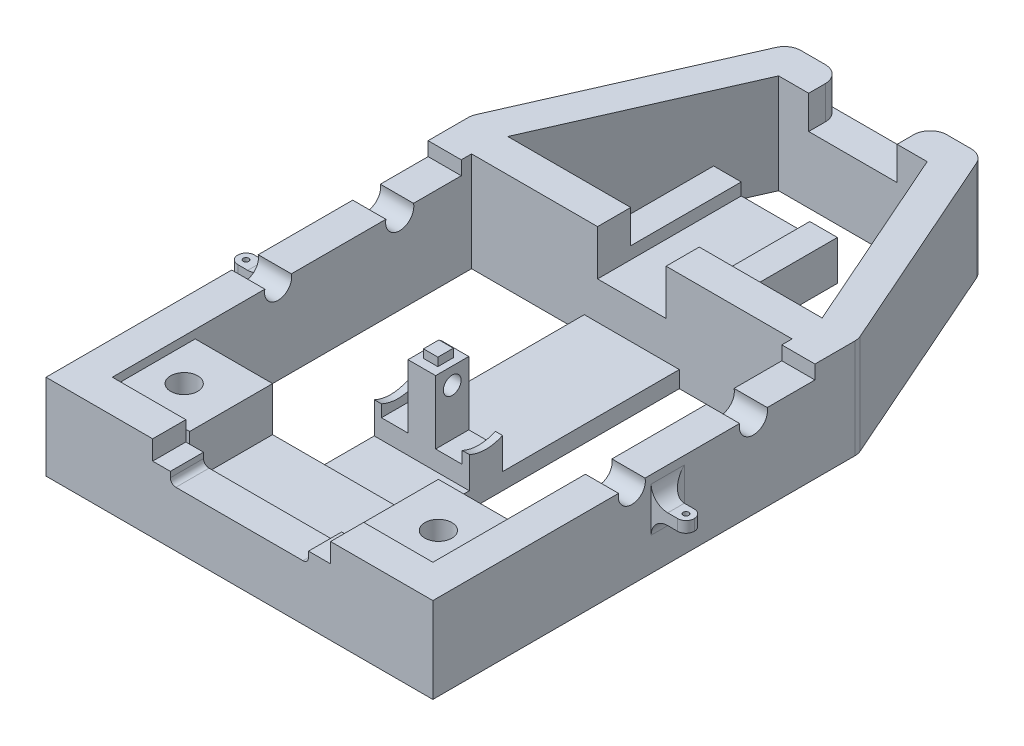
SolidWorks part; units mm, degrees
ref_plane "Front Plane" through (0, 0, 0) normal (0, 0, 1) x (1, 0, 0)
ref_plane "Top Plane" through (0, 0, 0) normal (0, 1, 0) x (1, 0, 0)
ref_plane "Right Plane" through (0, 0, 0) normal (1, 0, 0) x (0, 0, -1)
sketch "Sketch1" plane through (0, 0, 0) normal (0, 1, 0) x (1, 0, 0)
  line L0 (-35, 38.5) -> (-17.3529, 78.5)
  line L1 (-29, 32.5) -> (29, 32.5)
  line L2 (-29, 32.5) -> (-29, -32.5)
  line L3 (-29, -32.5) -> (29, -32.5)
  line L4 (29, 32.5) -> (29, -32.5)
  line L5 (-29, 32.5) -> (29, -32.5) construction
  line L6 (-29, -32.5) -> (29, 32.5) construction
  line L7 (-28.442, 38.5) -> (28.442, 38.5)
  line L8 (-35, 38.5) -> (-35, -38.5)
  line L9 (-35, -38.5) -> (35, -38.5)
  line L10 (35, 38.5) -> (35, -38.5)
  line L11 (-35, 38.5) -> (35, -38.5) construction
  line L12 (-35, -38.5) -> (35, 38.5) construction
  line L13 (-17.3529, 78.5) -> (17.3529, 78.5)
  line L14 (17.3529, 78.5) -> (35, 38.5)
  line L15 (-28.442, 38.5) -> (-13.442, 72.5)
  line L16 (-13.442, 72.5) -> (13.442, 72.5)
  line L17 (13.442, 72.5) -> (28.442, 38.5)
  point P0 (0, 0)
  point P6 (0, 0)
  point P15 (0, 72.5)
  point P18 (0, 38.5)
  dimension "D1" = 58
  dimension "D2" = 6
  dimension "D3" = 6
  dimension "D4" = 65
  dimension "D5" = 40
  dimension "D6" = 6
  dimension "D7" = 6
  dimension "D8" = 6
  dimension "D9" = 34
  dimension "D10" = 15
  dimension "D11" = 6
  dimension "D12" = 6
extrude "Boss-Extrude1" add sketch "Sketch1" along normal blind 30
ref_plane "Plane1" through (0, 0, 5.5) normal (0, 0, 1) x (1, 0, 0)
ref_plane "Plane2" through (0, 15, 0) normal (0, -1, 0) x (-1, 0, 0)
sketch "Sketch7" plane through (0, 0, -32.5) normal (0, 0, 1) x (1, 0, 0)
  line L0 (-35, 30) -> (35, 30) construction
  line L1 (-8.6, 30) -> (8.6, 30)
  line L2 (-8.6, 30) -> (-8.6, 27)
  line L3 (-8.6, 27) -> (8.6, 27)
  line L4 (8.6, 30) -> (8.6, 27)
  line L6 (-35, 30) -> (-35, 0) construction
  point P6 (0, 30)
  dimension "D1" = 3
  dimension "D2" = 17.2
  dimension "D3" = 35
sketch "Sketch8" plane through (0, 0, 5.5) normal (0, 0, 1) x (1, 0, 0)
  line L0 (-8.6, 30) -> (8.6, 30) construction
  line L1 (-8.6, 30) -> (8.6, 30)
  line L2 (-8.6, 30) -> (-8.6, 27)
  line L3 (-8.6, 27) -> (8.6, 27)
  line L4 (8.6, 30) -> (8.6, 27)
  line L5 (-8.6, 27) -> (8.6, 27) construction
sketch "Sketch9" plane through (0, 30, 0) normal (0, 1, 0) x (1, 0, 0)
  line L0 (10, 32.5) -> (2.5, -5.5)
  line L1 (-8.6, 32.5) -> (8.6, 32.5) construction
  line L2 (-8.6, -5.5) -> (8.6, -5.5) construction
  line L3 (-16.5058, -5.5) -> (16.5058, -5.5) construction
  line L4 (-10, 32.5) -> (-2.5, -5.5)
loft "Loft3" add profiles "Sketch7", "Sketch8"
mirror "Mirror3" about plane through (0, 15, 0) normal (0, -1, 0) of "Loft3"
sketch "Sketch10" plane through (0, 27, 0) normal (0, -1, 0) x (1, 0, 0)
  line L0 (-8.6, -32.5) -> (8.6, -32.5) construction
  line L1 (-2.5, 5.5) -> (2.5, 5.5)
  line L2 (-2.5, 5.5) -> (-2.5, -0.5)
  line L3 (-2.5, -0.5) -> (2.5, -0.5)
  line L4 (2.5, 5.5) -> (2.5, -0.5)
  line L6 (-8.6, 5.5) -> (8.6, 5.5) construction
  point P5 (2.5, 2.5)
  point P10 (0, 5.5)
  point P11 (0, 5.5)
  dimension "D1" = 5
  dimension "D2" = 35
  dimension "D3" = 0
  dimension "D4" = 0
extrude "Boss-Extrude3" add sketch "Sketch10" along normal up to next
sketch "Sketch2" plane through (35, 0, 0) normal (1, 0, 0) x (0, 0, -1)
  line L0 (38.5, 30) -> (38.5, 0) construction
  line L1 (-38.5, 30) -> (38.5, 30) construction
  circle A0 centre (-2.5, 15) radius 2.45
  circle A1 centre (19.5, 15) radius 2.55
  dimension "D2" = 15
  dimension "D3" = 4.9
  dimension "D5" = 5.1
  dimension "D1" = 19
  dimension "D4" = 22
extrude "Cut-Extrude1" cut sketch "Sketch2" against normal up to next
sketch "Sketch3" plane through (0, 0, -38.5) normal (0, 0, -1) x (-1, 0, 0)
  line L1 (-6.2, 20.2) -> (6.2, 20.2)
  line L2 (-6.2, 20.2) -> (-6.2, 9.8)
  line L3 (-6.2, 9.8) -> (6.2, 9.8)
  line L4 (6.2, 20.2) -> (6.2, 9.8)
  line L5 (-6.2, 20.2) -> (6.2, 9.8) construction
  line L6 (-6.2, 9.8) -> (6.2, 20.2) construction
  line L7 (-17.3529, 0) -> (17.3529, 0) construction
  line L9 (35, 30) -> (35, 0) construction
  point P0 (0, 15)
  dimension "D1" = 10.4
  dimension "D2" = 12.4
  dimension "D3" = 35
  dimension "D4" = 15
extrude "Cut-Extrude2" cut sketch "Sketch3" against normal up to next
sketch "Sketch11" plane through (35, 0, 0) normal (1, 0, 0) x (0, 0, -1)
  line L0 (-2.5, 15) -> (72.7738, 15) construction
  line L1 (1, 19) -> (4, 19)
  line L2 (1, 19) -> (1, 21)
  line L3 (1, 21) -> (4, 21)
  line L4 (4, 19) -> (4, 21)
  line L5 (4, 11) -> (4, 9)
  line L6 (1, 9) -> (4, 9)
  line L7 (1, 11) -> (1, 9)
  line L8 (1, 11) -> (4, 11)
  point P7 (2.5, 19)
  dimension "D1" = 3
  dimension "D2" = 2
  dimension "D3" = 6
  dimension "D4" = 5
extrude "Boss-Extrude4" add sketch "Sketch11" along normal blind 6.3
fillet "Fillet3" radius 1.5 4 edges at (41.3, 10, -1) (41.3, 10, -4) (41.3, 20, -1) (41.3, 20, -4)
sketch "Sketch12" plane through (0, 21, 0) normal (0, 1, 0) x (1, 0, 0)
  circle A0 centre (39.8, 2.5) radius 0.5
extrude "Cut-Extrude3" cut sketch "Sketch12" against normal through all
ref_plane "Plane3" through (0, 0, 0) normal (1, 0, 0) x (0, 0, -1)
mirror "Mirror1" about plane through (0, 0, 0) normal (1, 0, 0) of "Cut-Extrude1", "Boss-Extrude4", "Fillet3", "Cut-Extrude3"
sketch "Sketch13" plane through (-29, 0, 0) normal (1, 0, 0) x (0, 0, -1)
  line L1 (-32.5, 30) -> (-17.5, 30)
  line L2 (-32.5, 30) -> (-32.5, 24)
  line L3 (-32.5, 24) -> (-17.5, 24)
  line L4 (-17.5, 30) -> (-17.5, 24)
  dimension "D1" = 6
  dimension "D2" = 15
extrude "Boss-Extrude5" add sketch "Sketch13" along normal up to next
sketch "Sketch17" plane through (-29, 0, 0) normal (1, 0, 0) x (0, 0, -1)
  line L0 (32.5, 0) -> (-32.5, 0) construction
  line L1 (-32.5, 0) -> (-17.5, 0)
  line L2 (-32.5, 0) -> (-32.5, 14)
  line L3 (-32.5, 14) -> (-17.5, 14)
  line L4 (-17.5, 0) -> (-17.5, 14)
  dimension "D1" = 14
  dimension "D2" = 15
extrude "Boss-Extrude6" add sketch "Sketch17" along normal up to next
sketch "Sketch14" plane through (0, 30, 0) normal (0, 1, 0) x (1, 0, 0)
  line L0 (-35, 38.5) -> (-35, -38.5) construction
  line L1 (35, -38.5) -> (35, 38.5) construction
  line L2 (-35, -38.5) -> (35, -38.5) construction
  circle A0 centre (-23, -25.5) radius 2.45
  circle A1 centre (23, -25.5) radius 2.45
  dimension "D5" = 4.9
  dimension "D6" = 4.9
  dimension "D1" = 12
  dimension "D2" = 12
  dimension "D3" = 13
  dimension "D4" = 0
extrude "Cut-Extrude4" cut sketch "Sketch14" against normal through all
sketch "Sketch16" plane through (35, 0, 0) normal (1, 0, 0) x (0, 0, -1)
  line L0 (-38.5, 30) -> (-38.5, 0) construction
  line L7 (-38.5, 22.5) -> (-22.5, 22.5)
  line L8 (-38.5, 22.5) -> (-38.5, 15.5)
  line L9 (-38.5, 15.5) -> (-22.5, 15.5)
  line L10 (-22.5, 22.5) -> (-22.5, 15.5)
  line L11 (-38.5, 30) -> (38.5, 30) construction
  dimension "D1" = 7.5
  dimension "D2" = 7
  dimension "D3" = 16
extrude "Cut-Extrude7" cut sketch "Sketch16" against normal blind 15
mirror "Mirror2" about plane through (0, 0, 0) normal (1, 0, 0) of "Cut-Extrude7"
sketch "Sketch18" plane through (0, 0, 38.5) normal (0, 0, 1) x (1, 0, 0)
  line L0 (0, -16.5) -> (0, 16.5) construction
  line L3 (-35, 0) -> (35, 0) construction
  line L4 (-11.5, 14) -> (11.5, 14)
  line L5 (-11.5, 10) -> (11.5, 10)
  line L6 (-12.5, 13) -> (-12.5, 11)
  line L7 (12.5, 11) -> (12.5, 13)
  arc A2 (12.5, 11) -> (11.5, 10) centre (11.5, 11) cw
  arc A3 (12.5, 13) -> (11.5, 14) centre (11.5, 13) ccw
  arc A4 (-11.5, 10) -> (-12.5, 11) centre (-11.5, 11) cw
  arc A5 (-11.5, 14) -> (-12.5, 13) centre (-11.5, 13) ccw
  point P0 (0, 14)
  point P12 (12.5, 10)
  point P15 (12.5, 14)
  point P20 (-12.5, 14)
  dimension "D2" = 10
  dimension "D5" = 1
  dimension "D1" = 4
  dimension "D3" = 25
  dimension "D4" = 0
extrude "Cut-Extrude8" cut sketch "Sketch18" against normal up to next
sketch "Sketch19" plane through (0, 30, 0) normal (0, 1, 0) x (1, 0, 0)
  line L0 (29, -17.5) -> (-29, -17.5) construction
  line L1 (-15, -17.5) -> (15, -17.5)
  line L2 (-15, -17.5) -> (-15, -32.5)
  line L3 (-15, -32.5) -> (15, -32.5)
  line L4 (15, -17.5) -> (15, -32.5)
  line L5 (-35, -38.5) -> (35, -38.5) construction
  line L6 (-35, 38.5) -> (-35, -38.5) construction
  line L7 (35, -38.5) -> (35, 38.5) construction
  dimension "D1" = 6
  dimension "D2" = 20
  dimension "D3" = 20
extrude "Cut-Extrude9" cut sketch "Sketch19" against normal offset from surface (18 mm away) 6 from offset 6 up to face at (-23, 0, 27.95) offset against normal yes
sketch "Sketch35" plane through (0, 0, -78.5) normal (0, 0, -1) x (-1, 0, 0)
  line L0 (0, 0) -> (0, 30) construction
  line L1 (28.442, 30) -> (-28.442, 30) construction
  line L3 (-8, 18) -> (8, 18)
  line L4 (-8, 18) -> (-8, 12)
  line L5 (-8, 12) -> (8, 12)
  line L6 (8, 18) -> (8, 12)
  line L7 (-8, 18) -> (8, 12) construction
  line L8 (-8, 12) -> (8, 18) construction
  point P5 (0, 15)
  dimension "D1" = 16
  dimension "D2" = 6
extrude "Cut-Extrude18" cut sketch "Sketch35" against normal up to next
fillet "Fillet5" radius 3 6 edges at (-35, 15, -38.5) (-17.3529, 15, -78.5) (-8, 15, -78.5) (8, 15, -78.5) (17.3529, 15, -78.5) (35, 15, -38.5)
sketch "Sketch24" plane through (0, 0, 0) normal (0, 1, 0) x (1, 0, 0)
  line L0 (13.442, 72.5) -> (-13.442, 72.5) construction
  line L1 (-23.5891, 49.5) -> (-9.15, 49.5)
  line L3 (-26.2362, 43.5) -> (26.2362, 43.5)
  line L5 (28.442, 38.5) -> (13.442, 72.5) construction
  line L7 (-6.15, 49.5) -> (-6.15, 72.5)
  line L9 (6.15, 49.5) -> (6.15, 72.5)
  line L10 (-13.442, 72.5) -> (-28.442, 38.5) construction
  line L11 (26.2362, 43.5) -> (22.3466, 52.3162)
  line L12 (-23.5891, 49.5) -> (-26.2362, 43.5)
  line L13 (-6.15, 49.5) -> (6.15, 49.5)
  line L15 (-9.15, 49.5) -> (-9.15, 72.5)
  line L16 (-9.15, 72.5) -> (-6.15, 72.5)
  line L17 (-6.15, 49.5) -> (-6.15, 72.5)
  line L19 (6.15, 49.5) -> (6.15, 72.5)
  line L20 (6.15, 72.5) -> (9.15, 72.5)
  line L21 (9.15, 52.5) -> (9.15, 72.5)
  line L22 (9.15, 52.5) -> (22.3466, 52.3162)
  point P10 (0, 49.5)
  point P12 (0, 43.5)
  point P13 (0, 72.5)
  dimension "D1" = 23
  dimension "D2" = 6
  dimension "D4" = 0
  dimension "D5" = 12.3
  dimension "D7" = 3
  dimension "D8" = 3
extrude "Boss-Extrude7" add sketch "Sketch24" along normal up to surface (9.8 mm away) from offset 30 contours L21 L22 L11 L3 L12 L1 L15 L16 L7 L13 L9 L20
sketch "Sketch23" plane through (0, 12, 0) normal (0, 1, 0) x (1, 0, 0)
  line L1 (-6.15, 72.5) -> (6.15, 72.5)
  line L2 (-6.15, 72.5) -> (-6.15, 78.5)
  line L3 (-6.15, 78.5) -> (6.15, 78.5)
  line L4 (6.15, 72.5) -> (6.15, 78.5)
  line L5 (15.3975, 78.5) -> (-15.3975, 78.5) construction
  line L6 (-26.2362, 43.5) -> (26.2362, 43.5) construction
  line L7 (-6.15, 49.5) -> (6.15, 49.5)
  line L8 (-6.15, 49.5) -> (-6.15, 43.5)
  line L9 (-6.15, 43.5) -> (6.15, 43.5)
  line L10 (6.15, 49.5) -> (6.15, 43.5)
  point P8 (0, 78.5)
  point P9 (0, 72.5)
  dimension "D2" = 0
extrude "Cut-Extrude12" cut sketch "Sketch23" along normal up to next from offset 16.5
sketch "Sketch26" plane through (0, 0, -38.5) normal (0, 0, -1) x (-1, 0, 0)
  line L0 (-6.2, 9.8) -> (6.2, 9.8) construction
  line L1 (6.2, 9.8) -> (6.2, 20.2) construction
  line L2 (11, 12) -> (8, 12) construction
  line L3 (-6.2, 20.2) -> (-6.2, 9.8) construction
  line L4 (-6.2, 9.8) -> (6.2, 9.8)
  line L5 (6.2, 9.8) -> (6.2, 12)
  line L7 (-6.2, 12) -> (-6.2, 9.8)
  line L8 (-11.2, 4.8) -> (11.2, 4.8)
  line L9 (11.2, 4.8) -> (11.2, 12)
  line L11 (-11.2, 12) -> (-11.2, 4.8)
  line L12 (-11.2, 12) -> (-6.2, 12)
  line L14 (6.2, 12) -> (11.2, 12)
  line L15 (-11.2, 25.2) -> (-11.2, 4.8) construction
  line L16 (11.2, 25.2) -> (-11.2, 25.2) construction
  line L17 (6.2, 20.2) -> (-6.2, 20.2) construction
  line L18 (-6.2, 20.2) -> (-6.2, 9.8) construction
  line L19 (6.2, 9.8) -> (6.2, 20.2) construction
  line L20 (11.2, 4.8) -> (11.2, 25.2) construction
  line L21 (-11, 12) -> (11, 12) construction
  dimension "D1" = 5
extrude "Boss-Extrude8" add sketch "Sketch26" along normal blind 20
sketch "Sketch28" plane through (0, 28.5, 0) normal (0, 1, 0) x (-1, 0, 0)
  line L0 (0, 16.5) -> (0, -16.5) construction
  line L1 (0.4, -44) -> (6, -44) construction
  line L2 (0.4, -78) -> (6, -78) construction
  circle A0 centre (0, -46.5) radius 0.8
  circle A1 centre (0, -75.5) radius 0.8
  dimension "D2" = 1.6
  dimension "D3" = 1.6
  dimension "D1" = 2.5
  dimension "D4" = 2.5
extrude "Cut-Extrude15" cut sketch "Sketch28" against normal up to next
fillet "Fillet4" radius 3 12 edges at (35, 9, -2.5) (35, 11, -2.5) (35, 21, -2.5) (35, 19, -2.5) (35, 20, -4) (35, 10, -4) (-35, 9, -2.5) (-35, 10, -4) (-35, 11, -2.5) (-35, 19, -2.5) (-35, 20, -4) (-35, 21, -2.5)
sketch "Sketch29" plane through (2.5, 0, 0) normal (1, 0, 0) x (0, 0, -1)
  circle A0 centre (-2.5, 15) radius 1.6
  dimension "D1" = 3.2
extrude "Cut-Extrude16" cut sketch "Sketch29" against normal up to next
sketch "Sketch30" plane through (-2.5, 0, 0) normal (-1, 0, 0) x (0, 0, 1)
  line L0 (-32.5, 27) -> (5.5, 27) construction
  line L1 (-0.5, 27) -> (5.5, 27)
  line L2 (-0.5, 27) -> (-0.5, 23.5)
  line L3 (-0.5, 23.5) -> (5.5, 23.5)
  line L4 (5.5, 27) -> (5.5, 23.5)
  line L5 (-0.5, 3) -> (-0.5, 27) construction
  line L6 (5.5, 3) -> (5.5, 27) construction
  dimension "D1" = 3.5
extrude "Boss-Extrude9" add sketch "Sketch30" along normal blind 6.1
sketch "Sketch31" plane through (0, 23.5, 0) normal (0, -1, 0) x (1, 0, 0)
  line L0 (-8.6, -0.5) -> (-2.5, -0.5) construction
  line L1 (-8.6, 5.5) -> (-7.3, 5.5)
  line L2 (-8.6, 5.5) -> (-8.6, -0.5)
  line L3 (-8.6, -0.5) -> (-7.3, -0.5)
  line L4 (-7.3, 5.5) -> (-7.3, -0.5)
  dimension "D1" = 1.3
extrude "Boss-Extrude10" add sketch "Sketch31" along normal blind 5
sketch "Sketch32" plane through (-8.6, 0, 0) normal (-1, 0, 0) x (0, 0, 1)
  line L0 (-0.5, 18.5) -> (-0.5, 21.3246)
  line L1 (-0.5, 27) -> (-0.5, 18.5) construction
  line L2 (-0.5, 18.5) -> (5.5, 18.5)
  line L3 (5.5, 18.5) -> (5.5, 21.3246)
  line L4 (5.5, 18.5) -> (5.5, 27) construction
  arc A2 (5.5, 21.3246) -> (-0.5, 21.3246) centre (2.5, 15) ccw
  dimension "D1" = 7
extrude "Cut-Extrude17" cut sketch "Sketch32" against normal up to next
mirror "Mirror4" about plane through (0, 15, 0) normal (0, -1, 0) of "Cut-Extrude17", "Boss-Extrude10", "Boss-Extrude9"
mirror "Mirror5" about plane through (0, 0, 0) normal (1, 0, 0) of "Mirror4", "Cut-Extrude17", "Boss-Extrude10", "Boss-Extrude9"
sketch "Sketch33" plane through (0, 0, 5.5) normal (0, 0, 1) x (1, 0, 0)
  line L1 (-8.6, 30) -> (8.6, 30)
  line L2 (-8.6, 30) -> (-8.6, 27)
  line L3 (-8.6, 27) -> (8.6, 27)
  line L4 (8.6, 30) -> (8.6, 27)
  dimension "D1" = 3
sketch "Sketch34" plane through (0, 0, 17.5) normal (0, 0, -1) x (-1, 0, 0)
  line L0 (-29, 30) -> (29, 30) construction
  line L1 (-8.6, 30) -> (8.6, 30)
  line L2 (-8.6, 30) -> (-8.6, 27)
  line L3 (-8.6, 27) -> (8.6, 27)
  line L4 (8.6, 30) -> (8.6, 27)
  line L5 (0, 16.5) -> (0, -16.5) construction
  point P6 (0, 27)
  dimension "D3" = 0
loft "Loft4" add profiles "Sketch33", "Sketch34"
mirror "Mirror6" about plane through (0, 15, 0) normal (0, -1, 0) of "Loft4"
sketch3d "Cut_line"
  line L0 (35, 18, -78.5) -> (35, 18, -30.637)
  line L1 (35, 15.5, 38.5) -> (35, 15.5, -30.637)
  line L2 (35, 15.5, -30.637) -> (35, 18, -30.637)
  line L3 (35, 15.5, 38.5) -> (16.4919, 15.5, 38.5)
  line L4 (12.5, 12, 38.5) -> (16.4919, 12, 38.5)
  line L5 (12.5, 11, 38.5) -> (12.5, 13, 38.5) construction
  line L6 (16.4919, 12, 38.5) -> (16.4919, 15.5, 38.5)
  line L7 (12.5, 12, 38.5) -> (-15.6959, 12, 38.5)
  line L8 (-15.6959, 12, 38.5) -> (-15.6959, 15.5, 38.5)
  line L9 (-15.6959, 15.5, 38.5) -> (-35, 15.5, 38.5)
  line L10 (35, 18, -78.5) -> (-35, 18, -78.5)
  line L11 (-35, 18, -78.5) -> (-35, 18, -30.637)
  line L12 (-35, 18, -30.637) -> (-35, 15.5, -30.637)
  line L13 (-35, 15.5, -30.637) -> (-35, 15.5, 38.5)
  line L14 (-11, 18, -78.5) -> (11, 18, -78.5) construction
  dimension "D1" = 0
sketch "Sketch36" plane through (0, 30, 0) normal (0, 1, 0) x (1, 0, 0)
  line L1 (-79.7704, 95.6479) -> (84.8882, 95.6479)
  line L2 (-79.7704, 95.6479) -> (-79.7704, -54.2142)
  line L3 (-79.7704, -54.2142) -> (84.8882, -54.2142)
  line L4 (84.8882, 95.6479) -> (84.8882, -54.2142)
extrude "Cut-Extrude19" cut sketch "Sketch36" against normal blind 12
sketch "Sketch37" plane through (0, 18, 0) normal (0, 1, 0) x (1, 0, 0)
  line L1 (35, 30.637) -> (-54.071, 30.637)
  line L3 (35, -45.1136) -> (-54.071, -45.1136)
  line L4 (-54.071, 30.637) -> (-54.071, -45.1136)
  line L5 (35, 30.637) -> (52.4824, 30.637)
  line L7 (35, -45.1136) -> (52.4824, -45.1136)
  line L8 (52.4824, 30.637) -> (52.4824, -45.1136)
  line L9 (-2.5, -5.5) -> (2.5, -5.5)
  line L10 (-2.5, -5.5) -> (-2.5, 0.5)
  line L11 (-2.5, 0.5) -> (2.5, 0.5)
  line L12 (2.5, -5.5) -> (2.5, 0.5)
extrude "Cut-Extrude20" cut sketch "Sketch37" against normal blind 2.5
sketch "Sketch38" plane through (0, 15.5, 0) normal (0, 1, 0) x (1, 0, 0)
  line L0 (29, -32.5) -> (15, -32.5) construction
  line L1 (-15.6959, -38.5) -> (16.4919, -38.5)
  line L2 (-15.6959, -38.5) -> (-15.6959, -32.5)
  line L3 (-15.6959, -32.5) -> (16.4919, -32.5)
  line L4 (16.4919, -38.5) -> (16.4919, -32.5)
extrude "Cut-Extrude21" cut sketch "Sketch38" against normal blind 3.5
sketch "Sketch39" plane through (0, 18, 0) normal (0, 1, 0) x (1, 0, 0)
  line L0 (-2.5, -2.5) -> (2.5, -2.5) construction
  line L1 (-2.5, 0.5) -> (-2.5, -5.5) construction
  line L2 (2.5, -5.5) -> (2.5, 0.5) construction
  line L3 (-8.6, -5.5) -> (8.6, -5.5) construction
  line L4 (-1.3, -1.1) -> (1.3, -1.1)
  line L5 (-1.3, -1.1) -> (-1.3, -3.9)
  line L6 (-1.3, -3.9) -> (1.3, -3.9)
  line L7 (1.3, -1.1) -> (1.3, -3.9)
  line L8 (-1.3, -1.1) -> (1.3, -3.9) construction
  line L9 (-1.3, -3.9) -> (1.3, -1.1) construction
  point P6 (0, -2.5)
  point P13 (0, -5.5)
  dimension "D1" = 1.6
  dimension "D2" = 1.2
extrude "Boss-Extrude11" add sketch "Sketch39" along normal blind 1.5
